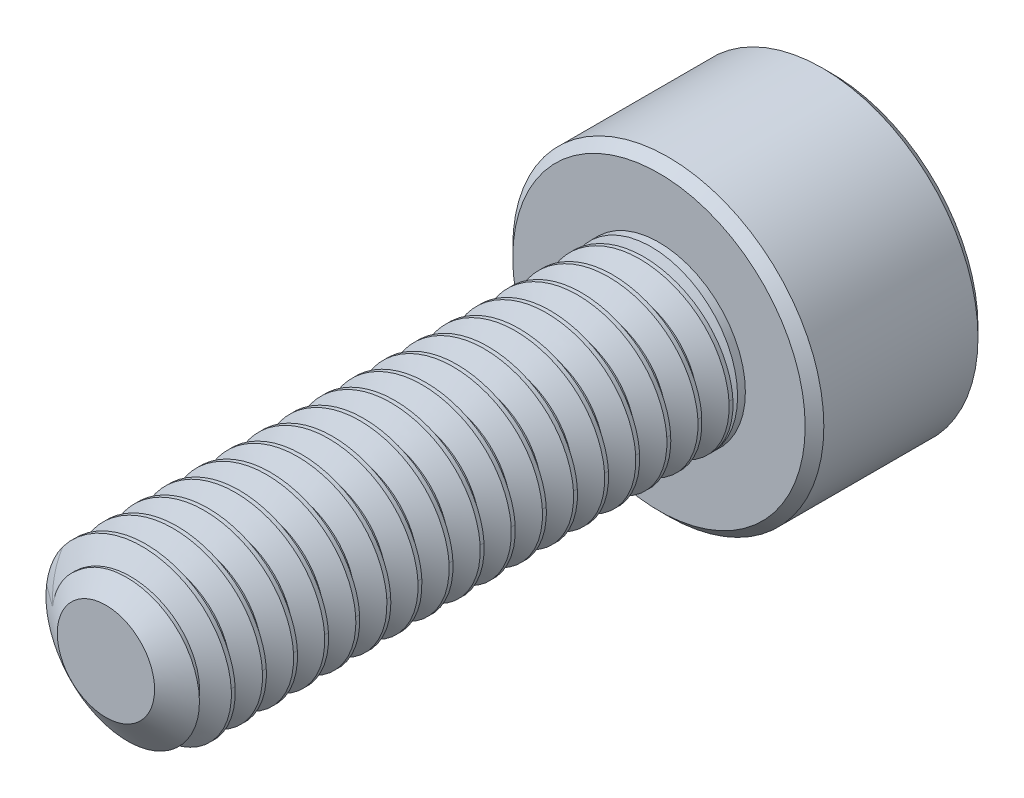
SolidWorks part; units mm, degrees
ref_plane "Front Plane" through (0, 0, 0) normal (0, 0, 1) x (1, 0, 0)
ref_plane "Top Plane" through (0, 0, 0) normal (0, 1, 0) x (1, 0, 0)
ref_plane "Right Plane" through (0, 0, 0) normal (1, 0, 0) x (0, 0, -1)
sketch "Sketch1" plane through (0, 0, 0) normal (0, 0, 1) x (1, 0, 0)
  circle A0 centre (0, 0) radius 1.25
  dimension "OD" = 2.5
extrude "Extrude1" add sketch "Sketch1" against normal blind 8
sketch "Sketch2" plane through (0, 0, 0) normal (0, 0, 1) x (1, 0, 0)
  circle A0 centre (0, 0) radius 1.25 construction
  circle A1 centre (0, 0) radius 1.25
curve "Helix/Spiral1" pitch 0.45 height 8.45 radius 1.25 centre (0, 0, 0) axis (0, 0, -1) start towards (0, 1, 0) parameters "pitch"=0.45
sketch "Sketch3" plane through (0, 0, 0) normal (1, 0, 0) x (0, 0, -1)
  line L0 (-0.3938, 1.25) -> (-0.225, 0.9577)
  line L1 (-0.225, 0.9577) -> (-0.1688, 0.9577)
  line L2 (-0.1688, 0.9577) -> (0, 1.25)
  line L3 (-0.3938, 1.25) -> (0, 1.25)
  line L4 (-0.1969, 1.25) -> (-0.1969, 0.9577) construction
  line L5 (-0.3094, 1.1039) -> (-0.0844, 1.1039) construction
  line L6 (0, 1.25) -> (0, -1.25) construction
  line L7 (0, -1.25) -> (8, -1.25) construction
  point P11 (2.025, -1.25)
  dimension "D1" = 0.0563
  dimension "D2" = 0.225
  dimension "D3" = 60
  dimension "D4" = 2.025
sweep "Cut-Sweep1" cut profiles "Sketch3" path "Helix/Spiral1" align with end faces yes
sketch "Sketch4" plane through (0, 0, 0) normal (1, 0, 0) x (0, 0, -1)
  line L0 (0.3825, 1.25) -> (0, 0.7037)
  line L1 (0, 0.7037) -> (0, 1.25)
  line L2 (0.3825, 1.25) -> (0, 1.25)
  line L3 (-0.3938, 1.25) -> (0, 1.25) construction
  line L4 (0, 0) -> (7.0209, 0) construction
  dimension "D1" = 55
  dimension "D2" = 0.254
revolve "Cut-Revolve1" cut sketch "Sketch4" angle 360 about L4
sketch "Sketch5" plane through (0, 0, 0) normal (1, 0, 0) x (0, 0, -1)
  line L0 (8, -1.1368) -> (8, -0.1596) construction
  line L1 (8, 1.25) -> (0.1203, 1.25)
  line L2 (8, 1.25) -> (8, 0)
  line L3 (8, 0) -> (0.0001, 0)
  line L4 (0.0001, 0.9198) -> (0.0001, 0)
  line L5 (0.1203, 1.25) -> (0.0001, 0.9198)
  line L6 (0, 0) -> (9.9695, 0) construction
  point P3 (0.0001, 1.25)
  point P10 (0.0001, 1.25)
  dimension "D1" = 0.3302
  dimension "Thread min" = 0.0001
  dimension "D3" = 20
revolve "partially thread" [suppressed] add sketch "Sketch5" angle 360 about L6
sketch "Sketch6" plane through (0, 0, -8) normal (0, 0, -1) x (-1, 0, 0)
  circle A0 centre (0, 0) radius 2.25
  dimension "head dia" = 4.5
extrude "Extrude2" add sketch "Sketch6" along normal blind 2.5
sketch "Sketch7" plane through (0, 0, -10.5) normal (0, 0, -1) x (-1, 0, 0)
  line L1 (0, 1.1547) -> (-1, 0.5774)
  line L2 (-1, 0.5774) -> (-1, -0.5774)
  line L3 (-1, -0.5774) -> (0, -1.1547)
  line L4 (0, -1.1547) -> (1, -0.5774)
  line L5 (1, -0.5774) -> (1, 0.5774)
  line L6 (1, 0.5774) -> (0, 1.1547)
  circle A0 centre (0, 0) radius 1 construction
  dimension "hex dia" = 2
extrude "Cut-Extrude1" cut sketch "Sketch7" against normal blind 1.5
sketch "Sketch8" plane through (0, 0, -10.5) normal (0, 0, -1) x (-1, 0, 0)
  circle A0 centre (0, 0) radius 1.1547
extrude "Cut-Extrude2" cut sketch "Sketch8" against normal through all draft 45
chamfer "Chamfer1" distance 0.135 angle 45 2 edges at (-2.25, 0, -10.5) (-2.25, 0, -8)
sketch "Sketch9" plane through (0, 0, 0) normal (1, 0, 0) x (0, 0, -1)
  line L0 (0, 1.25) -> (0, -1.25) construction
  line L1 (2.475, 1.25) -> (2.475, -1.25) construction
  dimension "D1" = 2.475
sketch "Sketch10" plane through (0, 0, 0) normal (1, 0, 0) x (0, 0, -1)
  line L0 (8, 1.25) -> (8, 0)
  line L1 (8, 1.25) -> (7.8875, 1.25)
  line L2 (7.8875, 1.25) -> (7.3697, 0)
  line L3 (8, 0) -> (7.3697, 0)
  line L4 (8, 2.115) -> (8, -2.115) construction
  dimension "D1" = 22.5
  dimension "D2" = 0.1125
revolve "Revolve1" add sketch "Sketch10" angle 360 about L3
equation "\"D3@Helix/Spiral1\" = \"screw length@Extrude1\"+\"pitch@Helix/Spiral1\""
equation "\"D1@Sketch3\" = \"pitch@Helix/Spiral1\"*.125"
equation "\"D2@Sketch3\" = \"pitch@Helix/Spiral1\"*.5"
equation "\"D1@Cut-Extrude1\" = \"hex dia@Sketch7\"*.75"
equation "\"D1@Chamfer1\" = \"head dia@Sketch6\"*.03"
equation "\"D1@Sketch9\" = \"pitch@Helix/Spiral1\"*5.5"
equation "\"D2@Sketch10\" = \"pitch@Helix/Spiral1\"*.25"
equation "\"D4@Sketch3\" = \"pitch@Helix/Spiral1\"*4.50"
